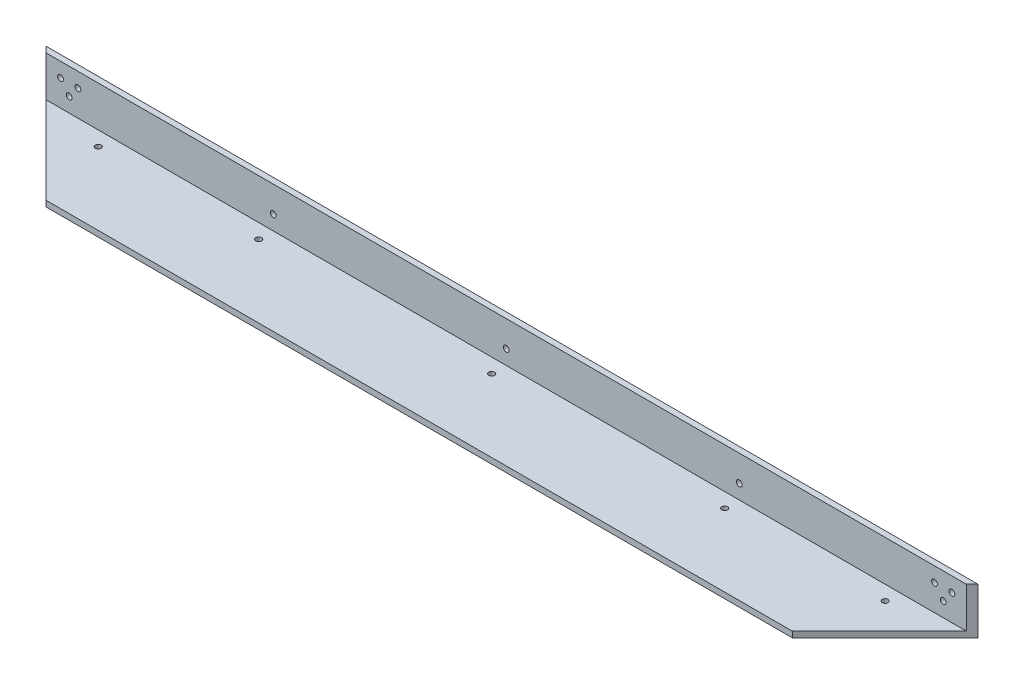
SolidWorks part; units mm, degrees
ref_plane "Front Plane" through (0, 0, 0) normal (0, 0, 1) x (1, 0, 0)
ref_plane "Top Plane" through (0, 0, 0) normal (0, 1, 0) x (1, 0, 0)
ref_plane "Right Plane" through (0, 0, 0) normal (1, 0, 0) x (0, 0, -1)
sketch "Sketch1" plane through (0, 0, 0) normal (1, 0, 0) x (0, 0, -1)
  line L0 (0, 0) -> (-50.8, 0)
  line L1 (-50.8, 0) -> (-50.8, 3.175)
  line L2 (-50.8, 3.175) -> (-3.175, 3.175)
  line L3 (-3.175, 3.175) -> (-3.175, 25.4)
  line L4 (-3.175, 25.4) -> (0, 25.4)
  line L5 (0, 25.4) -> (0, 0)
  dimension "LHeight" = 25.4
  dimension "LWidth" = 50.8
  dimension "LMaterialThickness" = 3.175
  dimension "D1" = 47.625
  dimension "D2" = 22.225
  dimension "D3" = 3.175
extrude "Boss-Extrude1" add sketch "Sketch1" along normal blind 510
chamfer "Chamfer6" distance 50.8 angle 45 1 edges at (510, 1.5875, 50.8)
chamfer "Chamfer7" distance 50.8 angle 45 1 edges at (0, 1.5875, 50.8)
sketch "BackSideHoles-Sketch2" plane through (0, 0, 0) normal (0, 0, -1) x (-1, 0, 0)
  line L0 (0, 0) -> (0, 25.4) construction
  line L1 (-510, 0) -> (0, 0) construction
  line L2 (-510, 0) -> (-510, 25.4) construction
  line L3 (-510, 25.4) -> (0, 25.4) construction
  circle A0 centre (-498.8875, 17.4625) radius 1.5875
  circle A1 centre (-489.3625, 17.4625) radius 1.5875
  circle A2 centre (-20.6375, 17.4625) radius 1.5875
  circle A4 centre (-11.1125, 17.4625) radius 1.5875
  circle A5 centre (-15.875, 11.1125) radius 1.5875
  circle A6 centre (-494.125, 11.1125) radius 1.5875
  circle A8 centre (-382.5, 11.1125) radius 1.5875
  circle A9 centre (-255, 11.1125) radius 1.5875
  circle A10 centre (-127.5, 11.1125) radius 1.5875
  point P6 (0, 0)
  dimension "D5" = 3.175
  dimension "D2" = 20.6375
  dimension "D4" = 20.6375
  dimension "D8" = 127.5
  dimension "D9" = 127.5
  dimension "D10" = 127.5
  dimension "D11" = 11.1125
  dimension "D6" = 7.9375
  dimension "D7" = 11.1125
  dimension "D3" = 11.1125
  dimension "D12" = 15.875
  dimension "D13" = 15.875
sketch "BottomHoles-Sketch3" plane through (0, 0, 0) normal (0, -1, 0) x (1, 0, 0)
  line L0 (510, 0) -> (0, 0) construction
  circle A7 centre (39.6875, 11.1125) radius 1.5875
  circle A8 centre (470.3125, 11.1125) radius 1.5875
  circle A9 centre (127.5, 11.1125) radius 1.5875
  circle A10 centre (255, 11.1125) radius 1.5875
  circle A11 centre (382.5, 11.1125) radius 1.5875
  dimension "D5" = 3.175
  dimension "D2" = 39.6875
  dimension "D3" = 39.6875
  dimension "D4" = 11.1125
  dimension "D1" = 127.5
  dimension "D6" = 127.5
  dimension "D7" = 127.5
extrude "BottomHoles-Cut-Extrude1" cut sketch "BottomHoles-Sketch3" against normal through all
extrude "BackSideHoles-Cut-Extrude2" cut sketch "BackSideHoles-Sketch2" against normal through all
equation "\"LowerRailWidth\"= 2.00in"
equation "\"LowerRailHeight\"= 1.00in"
equation "\"RailThickness\"= .125in'Spec"
equation "\"SideRailHoleX1FromSide\"= \"HoleOffsetFromSide\""
equation "\"SideRailHoleX2FromSide\"= \"VSWidth\" - \"HoleOffsetFromEdge\" - \"RailThickness\"'Equals 20.6375"
equation "\"SideRailHoleY1FromEdge\"= \"HoleOffsetFromEdge\""
equation "\"FrontBackRailLength\"= 510mm"
equation "\"VSWidth\"= 1.25in'Spec"
equation "\"HoleOffsetFromEdge\"= \"RailThickness\" * 2.5"
equation "\"HoleOffsetFromSide\"= \"RailThickness\" * 3.5"
equation "\"SideRailHoleY2FromSide\"= \"HoleOffsetFromSide\""
equation "\"FasteningHoleDiameter\"= .125in"
equation "\"D1@Boss-Extrude1\"=\"FrontBackRailLength\""
equation "\"D1@Chamfer6\"=\"LowerRailWidth\""
equation "\"D1@Chamfer7\"=\"LowerRailWidth\""
equation "\"D2@BackSideHoles-Sketch2\" = \"SideRailHoleX2FromSide\""
equation "\"D4@BackSideHoles-Sketch2\" = \"SideRailHoleX2FromSide\""
equation "\"D5@BackSideHoles-Sketch2\" = \"FasteningHoleDiameter\""
equation "\"LHeight@Sketch1\"=\"LowerRailHeight\""
equation "\"LWidth@Sketch1\"=\"LowerRailWidth\""
equation "\"LowerCornerBlockWidth\"= \"LowerRailWidth\" - \"RailThickness\" * 2'Room for left front stepper"
equation "\"D2@BottomHoles-Sketch3\"=\"CornerEnclosureOffset\""
equation "\"D3@BottomHoles-Sketch3\"=\"CornerEnclosureOffset\""
equation "\"D4@BottomHoles-Sketch3\"=\"LowerCornerBlockY1FromSide\""
equation "\"D5@BottomHoles-Sketch3\"=\"FasteningHoleDiameter\""
equation "\"CornerEnclosureOffset\"= \"LowerCornerBlockWidth\" - \"HoleOffsetFromEdge\" + \"RailThickness\""
equation "\"LowerCornerBlockY1FromSide\"= \"HoleOffsetFromSide\""
equation "\"FrontOrBackEnclosureOffsets\"= \"FrontBackRailLength\" / 4"
equation "\"D1@BottomHoles-Sketch3\"=\"FrontOrBackEnclosureOffsets\""
equation "\"D6@BottomHoles-Sketch3\"=\"FrontOrBackEnclosureOffsets\""
equation "\"D7@BottomHoles-Sketch3\"=\"FrontOrBackEnclosureOffsets\""
equation "\"D8@BackSideHoles-Sketch2\"=\"FrontOrBackEnclosureOffsets\""
equation "\"D9@BackSideHoles-Sketch2\"=\"FrontOrBackEnclosureOffsets\""
equation "\"D10@BackSideHoles-Sketch2\"=\"FrontOrBackEnclosureOffsets\""
equation "\"D11@BackSideHoles-Sketch2\"=\"SideRailHoleX1FromSide\""
equation "\"D6@BackSideHoles-Sketch2\"=\"SideRailHoleY1FromEdge\""
equation "\"D7@BackSideHoles-Sketch2\"=\"SideRailHoleY2FromSide\""
equation "\"D3@BackSideHoles-Sketch2\"=\"SideRailHoleX1FromSide\""
equation "\"VSMidSideRailHoleXFromSideToCenter\"= \"RailThickness\" * 6"
equation "\"D12@BackSideHoles-Sketch2\"=\"VSMidSideRailHoleXFromSideToCenter\" - \"RailThickness\""
equation "\"D13@BackSideHoles-Sketch2\"=\"VSMidSideRailHoleXFromSideToCenter\" - \"RailThickness\""
